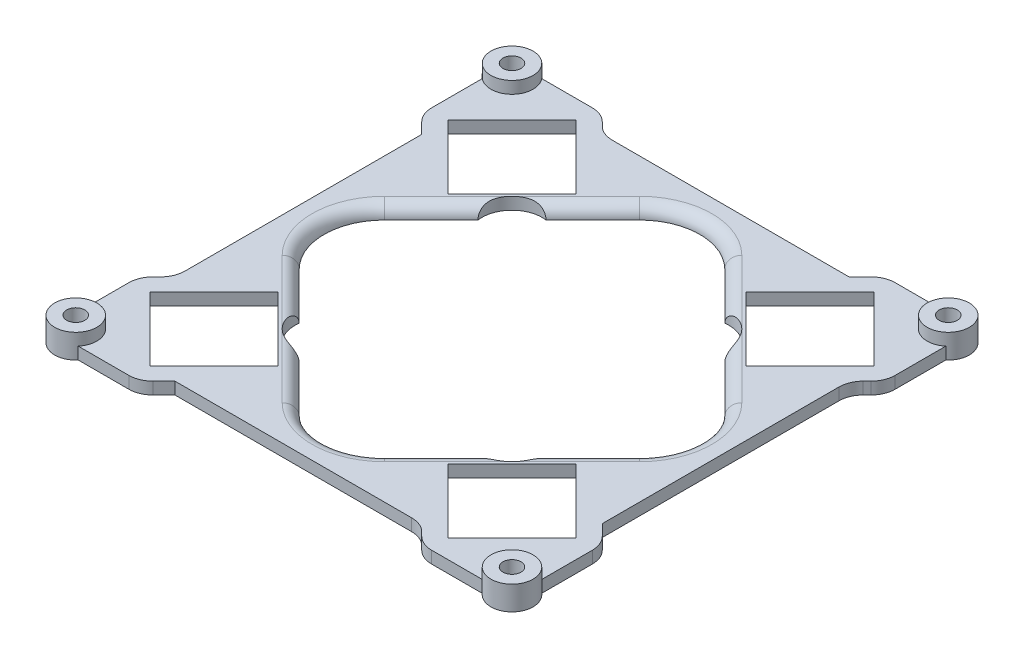
SolidWorks part; units mm, degrees
ref_plane "Front Plane" through (0, 0, 0) normal (0, 0, 1) x (1, 0, 0)
ref_plane "Top Plane" through (0, 0, 0) normal (0, 1, 0) x (1, 0, 0)
ref_plane "Right Plane" through (0, 0, 0) normal (1, 0, 0) x (0, 0, -1)
sketch "Sketch1" plane through (0, 0, 0) normal (0, 1, 0) x (1, 0, 0)
  line L0 (0, 0) -> (24.7487, 24.7487) construction
  line L1 (14.1421, 24.7487) -> (24.7487, 14.1421)
  line L2 (24.7487, 14.1421) -> (35.3553, 24.7487)
  line L3 (35.3553, 24.7487) -> (24.7487, 35.3553)
  line L4 (24.7487, 35.3553) -> (14.1421, 24.7487)
  line L5 (0, 0) -> (0, 31.0366) construction
  line L6 (-24.7487, 14.1421) -> (-35.3553, 24.7487)
  line L7 (-24.7487, 35.3553) -> (-14.1421, 24.7487)
  line L8 (-14.1421, 24.7487) -> (-24.7487, 14.1421)
  line L9 (-35.3553, 24.7487) -> (-24.7487, 35.3553)
  line L10 (0, 0) -> (19.4454, 0) construction
  line L11 (-14.1421, -24.7487) -> (-24.7487, -14.1421)
  line L12 (-24.7487, -14.1421) -> (-35.3553, -24.7487)
  line L13 (-35.3553, -24.7487) -> (-24.7487, -35.3553)
  line L14 (-24.7487, -35.3553) -> (-14.1421, -24.7487)
  line L15 (14.1421, -24.7487) -> (24.7487, -14.1421)
  line L16 (24.7487, -35.3553) -> (14.1421, -24.7487)
  line L17 (35.3553, -24.7487) -> (24.7487, -35.3553)
  line L18 (24.7487, -14.1421) -> (35.3553, -24.7487)
  line L19 (19.4454, 30.052) -> (30.052, 19.4454) construction
  line L20 (-38.5, 38.5) -> (38.5, 38.5)
  line L21 (-38.5, 38.5) -> (-38.5, -38.5)
  line L22 (-38.5, -38.5) -> (38.5, -38.5)
  line L23 (38.5, 38.5) -> (38.5, -38.5)
  dimension "D1" = 35
  dimension "D2" = 45
  dimension "D3" = 15
  dimension "D4" = 15
  dimension "D5" = 77
  dimension "D6" = 77
extrude "Boss-Extrude1" add sketch "Sketch1" along normal blind 2
sketch "Sketch2" plane through (0, 0, 0) normal (0, 1, 0) x (1, 0, 0)
  line L0 (0, 0) -> (16.8309, -16.8309) construction
  line L1 (35.3553, 0) -> (0, 35.3553)
  line L2 (35.3553, 0) -> (0, -35.3553)
  line L3 (0, -35.3553) -> (-35.3553, 0)
  line L4 (0, 35.3553) -> (-35.3553, 0)
  line L5 (0, 0) -> (11.6227, 11.6227) construction
  line L6 (0, 0) -> (0, -53.8912) construction
  dimension "D1" = 50
  dimension "D2" = 50
  dimension "D3" = 45
sketch "Sketch3" plane through (0, 0, 0) normal (0, 1, 0) x (1, 0, 0)
  line L0 (0, 0) -> (-36.2392, 36.2392) construction
  line L6 (0, 0) -> (-84.8053, 0) construction
  line L7 (0, 0) -> (0, 53.9683) construction
  circle A0 centre (-36.2392, 36.2392) radius 3.5
  circle A1 centre (36.2392, 36.2392) radius 3.5
  circle A2 centre (-36.2392, -36.2392) radius 3.5
  circle A3 centre (36.2392, -36.2392) radius 3.5
  dimension "D2" = 7
  dimension "D1" = 102.5
  dimension "D4" = 45
extrude "Boss-Extrude2" add sketch "Sketch3" along normal blind 4
sketch "Sketch4" plane through (0, 0, 0) normal (0, 1, 0) x (1, 0, 0)
  line L0 (-38.5, 23.5) -> (-38.5, -23.5)
  line L1 (-38.5, 33.5674) -> (-38.5, -33.5674) construction
  line L2 (-38.5, -23.5) -> (-35.5, -20.5)
  line L4 (-35.5, 20.5) -> (-38.5, 23.5)
  line L5 (0, 0) -> (-38.5, 0) construction
  line L6 (-35.5, 20.5) -> (-35.5, -20.5)
  line L7 (-24.7487, -14.1421) -> (-35.3553, -24.7487) construction
  dimension "D1" = 47
  dimension "D2" = 3
sketch "Sketch5" plane through (0, 0, 0) normal (0, 1, 0) x (1, 0, 0)
  circle A0 centre (0, 0) radius 1.5
  dimension "D1" = 3
extrude "Cut-Extrude1" cut sketch "Sketch5" along normal through all
extrude "Cut-Extrude3" cut sketch "Sketch4" along normal blind 5
pattern_circular "CirPattern3" count 4 over 360 about axis through (0, 4, 0) along (0, -1, 0) of "Cut-Extrude3"
fillet "Fillet3" radius 4 12 edges at (-23.5, 1, 38.5) (23.5, 1, 38.5) (38.5, 1, 23.5) (38.5, 1, -23.5) (23.5, 1, -38.5) (-23.5, 1, -38.5) (-38.5, 1, -23.5) (-38.5, 1, 23.5) (-20.5, 1, -35.5) (35.5, 1, -20.5) (20.5, 1, 35.5) (-35.5, 1, 20.5)
extrude "Cut-Extrude5" cut sketch "Sketch2" along normal blind 5
sketch "Sketch6" plane through (0, 0, 0) normal (0, 1, 0) x (1, 0, 0)
  line L12 (0, 0) -> (0, 107.8124) construction
  line L13 (0, 0) -> (48.224, 48.224) construction
  line L14 (0, 0) -> (27.59, -27.59) construction
  circle A0 centre (-36.2392, 36.2392) radius 1.5
  circle A1 centre (-36.2392, -36.2392) radius 1.5
  circle A2 centre (36.2392, -36.2392) radius 1.5
  circle A3 centre (36.2392, 36.2392) radius 1.5
  circle A4 centre (36.2392, 36.2392) radius 3.5 construction
  circle A5 centre (-36.2392, 36.2392) radius 3.5 construction
  circle A6 centre (-36.2392, -36.2392) radius 3.5 construction
  dimension "D3" = 3
extrude "Cut-Extrude6" cut sketch "Sketch6" along normal through all
fillet "Fillet4" radius 10 4 edges at (0, 1, -35.3553) (0, 1, 35.3553) (-35.3553, 1, 0) (35.3553, 1, 0)
sketch "Sketch8" plane through (0, 2, 0) normal (0, 1, 0) x (1, 0, 0)
  line L0 (0, 0) -> (15.5563, 15.5563) construction
  line L1 (0, 0) -> (-15.5563, 15.5563) construction
  line L2 (0, 0) -> (61.9561, 0) construction
  line L3 (0, 0) -> (0, 48.0989) construction
  circle A0 centre (15.5563, 15.5563) radius 5
  circle A1 centre (-15.5563, 15.5563) radius 5
  circle A2 centre (-15.5563, -15.5563) radius 5
  circle A3 centre (15.5563, -15.5563) radius 5
  dimension "D2" = 10
  dimension "D1" = 22
  dimension "D3" = 45
extrude "Cut-Extrude7" cut sketch "Sketch8" against normal blind 10
fillet "Fillet5" radius 2 12 edges at (-24.3952, 2, 10.9602) (-24.3952, 2, -10.9602) (10.9602, 2, 24.3952) (-10.9602, 2, 24.3952) (24.3952, 2, -10.9602) (24.3952, 2, 10.9602) (-10.9602, 2, -24.3952) (10.9602, 2, -24.3952) (-31.2132, 2, 0) (0, 2, 31.2132) (31.2132, 2, 0) (0, 2, -31.2132)
